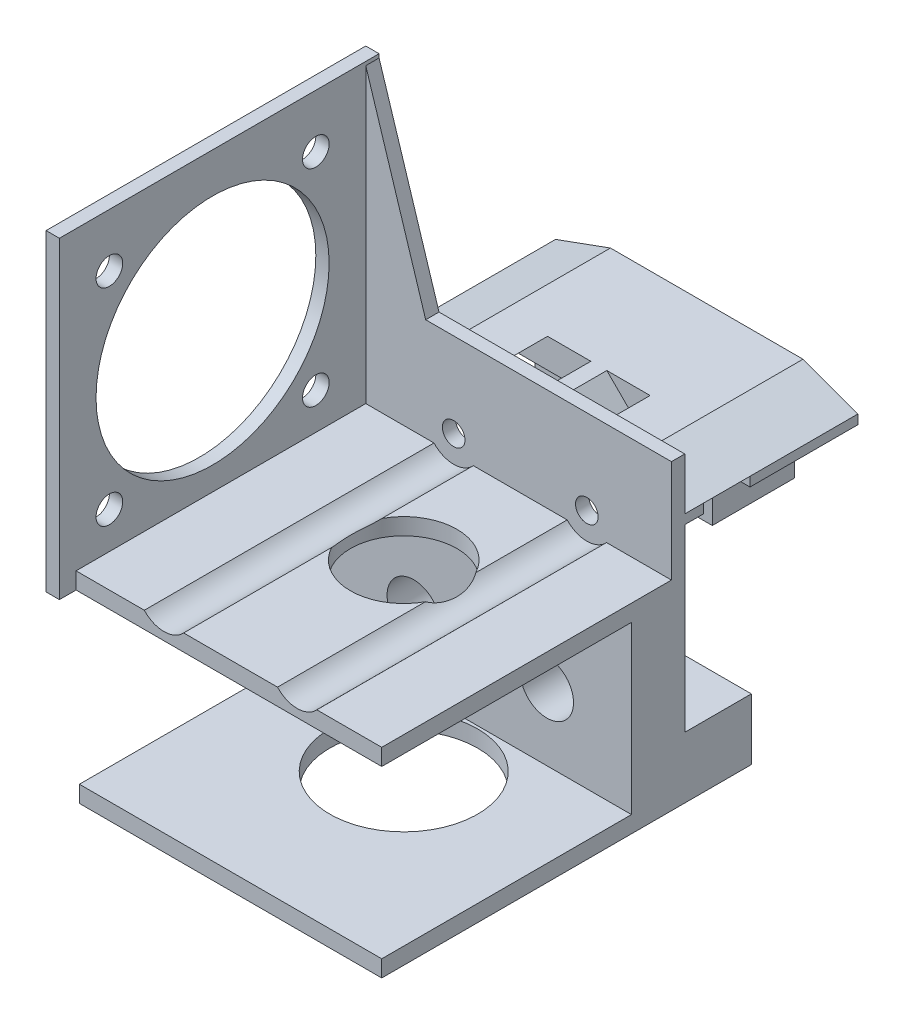
SolidWorks part; units mm, degrees
ref_plane "Front Plane" through (0, 0, 0) normal (0, 0, 1) x (1, 0, 0)
ref_plane "Top Plane" through (0, 0, 0) normal (0, 1, 0) x (1, 0, 0)
ref_plane "Right Plane" through (0, 0, 0) normal (1, 0, 0) x (0, 0, -1)
sketch "Sketch1" plane through (0, 0, 0) normal (0, 0, 1) x (1, 0, 0)
  line L1 (0, 0) -> (45.4, 0)
  line L2 (0, 0) -> (0, 45.4)
  line L3 (0, 45.4) -> (45.4, 45.4)
  line L4 (45.4, 0) -> (45.4, 45.4)
  dimension "D1" = 45.4
  dimension "D2" = 45.4
extrude "Boss-Extrude1" add sketch "Sketch1" along normal blind 12
sketch "Sketch2" plane through (0, 0, 0) normal (0, 0, -1) x (-1, 0, 0)
  line L0 (-45.4, 0) -> (-45.4, 45.4) construction
  line L1 (-45.4, 36.2) -> (0, 36.2)
  line L2 (-45.4, 36.2) -> (-45.4, 9.2)
  line L3 (-45.4, 9.2) -> (0, 9.2)
  line L4 (0, 36.2) -> (0, 9.2)
  line L5 (0, 45.4) -> (0, 0) construction
  line L6 (-45.4, 22.7) -> (0, 22.7) construction
  point P13 (-45.4, 22.7)
  dimension "D1" = 27
extrude "Cut-Extrude1" cut sketch "Sketch2" against normal blind 10
sketch "Sketch13" plane through (0, 0, 12) normal (0, 0, 1) x (1, 0, 0)
  line L0 (22.7, 45.4) -> (22.7, 0) construction
  line L1 (32.7, 12.7) -> (12.7, 12.7) construction
  line L2 (32.7, 12.7) -> (32.7, 32.7) construction
  line L3 (32.7, 32.7) -> (12.7, 32.7) construction
  line L4 (12.7, 12.7) -> (12.7, 32.7) construction
  line L5 (32.7, 12.7) -> (12.7, 32.7) construction
  line L6 (32.7, 32.7) -> (12.7, 12.7) construction
  line L7 (45.4, 45.4) -> (0, 45.4) construction
  line L8 (0, 0) -> (45.4, 0) construction
  line L9 (0, 22.7) -> (45.4, 22.7) construction
  line L10 (0, 9.2) -> (0, 36.2) construction
  line L11 (45.4, 36.2) -> (45.4, 9.2) construction
  circle A4 centre (32.7, 32.7) radius 1.7
  circle A5 centre (12.7, 32.7) radius 1.7
  circle A6 centre (32.7, 12.7) radius 1.7
  circle A7 centre (12.7, 12.7) radius 1.7
  point P12 (22.7, 22.7)
  point P31 (22.7, 22.7)
  dimension "D1" = 3.4
  dimension "D2" = 20
  dimension "D3" = 20
extrude "Cut-Extrude4" cut sketch "Sketch13" against normal up to next
sketch "Sketch20" plane through (45.4, 0, 0) normal (1, 0, 0) x (0, 0, -1)
  line L1 (-7.2, 36.2) -> (-0.2, 36.2)
  line L2 (-7.2, 36.2) -> (-7.2, 37.6)
  line L3 (-7.2, 37.6) -> (-0.2, 37.6)
  line L4 (-0.2, 36.2) -> (-0.2, 37.6)
  line L5 (-10, 36.2) -> (0, 36.2) construction
  line L6 (0, 36.2) -> (0, 45.4) construction
  dimension "D1" = 1.4
  dimension "D2" = 0.2
  dimension "D3" = 7
extrude "Cut-Extrude10" cut sketch "Sketch20" against normal blind 15
sketch "Sketch21" plane through (45.4, 0, 0) normal (1, 0, 0) x (0, 0, -1)
  line L0 (-0.2, 37.6) -> (-7.2, 37.6) construction
  line L1 (0, 45.4) -> (-10, 45.4)
  line L2 (0, 45.4) -> (0, 40.6)
  line L3 (0, 40.6) -> (-10, 40.6)
  line L4 (-10, 45.4) -> (-10, 40.6)
  dimension "D1" = 10
  dimension "D2" = 3
extrude "Cut-Extrude11" cut sketch "Sketch21" against normal through all
sketch "Sketch22" plane through (0, 0, 0) normal (-1, 0, 0) x (0, 0, 1)
  line L0 (10, 36.2) -> (0, 36.2) construction
  line L1 (0.2, 36.2) -> (7.2, 36.2)
  line L2 (0.2, 36.2) -> (0.2, 37.6)
  line L3 (0.2, 37.6) -> (7.2, 37.6)
  line L4 (7.2, 36.2) -> (7.2, 37.6)
  line L5 (0, 40.6) -> (0, 36.2) construction
  dimension "D1" = 7
  dimension "D2" = 0.2
  dimension "D3" = 1.4
extrude "Cut-Extrude12" cut sketch "Sketch22" against normal blind 15
sketch "Sketch29" plane through (0, 0, 12) normal (0, 0, 1) x (1, 0, 0)
  line L0 (0, 0) -> (45.4, 0) construction
  line L1 (0, 0) -> (45.4, 0)
  line L2 (0, 0) -> (0, 30)
  line L3 (0, 30) -> (45.4, 30)
  line L4 (45.4, 0) -> (45.4, 30)
  line L5 (0, 45.4) -> (0, 0) construction
  line L7 (22.7, 45.4) -> (22.7, 0) construction
  line L8 (45.4, 45.4) -> (0, 45.4) construction
  dimension "D3" = 30
extrude "Boss-Extrude6" add sketch "Sketch29" along normal blind 43.5
sketch "Sketch26" plane through (0, 0, 0) normal (0, 0, -1) x (-1, 0, 0)
  line L1 (-45.4, 40.6) -> (0, 40.6)
  line L2 (-45.4, 40.6) -> (-45.4, 36.2)
  line L3 (-45.4, 36.2) -> (0, 36.2)
  line L4 (0, 40.6) -> (0, 36.2)
  line L5 (0, 36.2) -> (-45.4, 36.2) construction
  line L6 (-45.4, 36.2) -> (-45.4, 40.6) construction
  line L7 (0, 40.6) -> (0, 36.2) construction
  line L8 (0, 40.6) -> (-45.4, 40.6) construction
extrude "Boss-Extrude4" add sketch "Sketch26" along normal blind 16
sketch "Sketch23" plane through (0, 40.6, 0) normal (0, 1, 0) x (1, 0, 0)
  line L1 (30.4, -0.2) -> (28.4, -0.2)
  line L2 (30.4, -0.2) -> (30.4, -7.2)
  line L3 (30.4, -7.2) -> (28.4, -7.2)
  line L4 (28.4, -0.2) -> (28.4, -7.2)
  line L5 (17, -7.2) -> (15, -7.2)
  line L6 (17, -7.2) -> (17, -0.2)
  line L7 (17, -0.2) -> (15, -0.2)
  line L8 (15, -7.2) -> (15, -0.2)
  line L9 (45.4, -10) -> (45.4, 16) construction
  line L10 (0, -10) -> (0, 16) construction
  line L13 (0, -10) -> (45.4, -10) construction
  dimension "D1" = 2
  dimension "D2" = 2
  dimension "D3" = 7
  dimension "D4" = 7
  dimension "D5" = 2.8
  dimension "D7" = 15
  dimension "D8" = 15
extrude "Cut-Extrude13" cut sketch "Sketch23" along normal blind 15 and the other way blind 15
sketch "Sketch17" plane through (0, 0, 12) normal (0, 0, 1) x (1, 0, 0)
  line L1 (12.7, 12.7) -> (32.7, 12.7) construction
  line L2 (12.7, 12.7) -> (12.7, 32.7) construction
  line L3 (12.7, 32.7) -> (32.7, 32.7) construction
  line L4 (32.7, 12.7) -> (32.7, 32.7) construction
  line L5 (12.7, 12.7) -> (32.7, 32.7) construction
  line L6 (12.7, 32.7) -> (32.7, 12.7) construction
  line L9 (22.7, 45.4) -> (22.7, 0) construction
  line L10 (45.4, 45.4) -> (0, 45.4) construction
  circle A0 centre (12.7, 32.7) radius 4
  circle A4 centre (32.7, 32.7) radius 4
  circle A5 centre (32.7, 12.7) radius 4
  circle A6 centre (12.7, 12.7) radius 4
  point P12 (22.7, 22.7)
  dimension "D1" = 8
  dimension "D2" = 20
  dimension "D3" = 20
extrude "Cut-Extrude8" cut sketch "Sketch17" along normal through all
chamfer "Chamfer1" distance 3 angle 70 1 edges at (45.4, 40.6, -3) first distance on face at (45.4, 29.4, 9.8625)
chamfer "Chamfer2" distance 3 angle 70 1 edges at (0, 40.6, -3) first distance on face at (0, 29.4, 9.8625)
sketch "Sketch24" plane through (0, 0, 0) normal (0, 0, -1) x (-1, 0, 0)
  line L0 (0, 0) -> (-45.4, 0) construction
  line L1 (-12, 0) -> (-10, 0)
  line L2 (-12, 0) -> (-12, 9.2)
  line L3 (-12, 9.2) -> (-10, 9.2)
  line L4 (-10, 0) -> (-10, 9.2)
  line L5 (-45.4, 9.2) -> (0, 9.2) construction
  line L6 (0, 9.2) -> (0, 0) construction
  dimension "D1" = 2
  dimension "D2" = 10
extrude "Boss-Extrude2" add sketch "Sketch24" along normal blind 10.25
sketch "Sketch25" plane through (10, 0, 0) normal (-1, 0, 0) x (0, 0, 1)
  line L0 (-10.25, 0) -> (0, 0) construction
  line L1 (-10.25, 9.2) -> (-8.75, 9.2)
  line L2 (-10.25, 9.2) -> (-10.25, 0)
  line L3 (-10.25, 0) -> (-8.75, 0)
  line L4 (-8.75, 9.2) -> (-8.75, 0)
  dimension "D1" = 1.5
extrude "Boss-Extrude3" add sketch "Sketch25" along normal blind 10
fillet "Fillet1" radius 4 2 edges at (12, 4.6, -10.25) (10, 4.6, -8.75)
chamfer "Chamfer3" distance 3 angle 45 2 edges at (15, 37.6, 3.7) (30.4, 37.6, 3.7)
chamfer "Chamfer4" distance 4.5 angle 45 2 edges at (28.4, 40.6, 3.7) (17, 40.6, 3.7)
sketch "Sketch27" plane through (0, 36.2, 0) normal (0, -1, 0) x (1, 0, 0)
  line L0 (45.4, -16) -> (0, -16) construction
  line L1 (35.878, -16) -> (9.2478, -16)
  line L2 (35.878, -16) -> (35.878, -3.6551)
  line L3 (35.878, -3.6551) -> (9.2478, -3.6551)
  line L4 (9.2478, -16) -> (9.2478, -3.6551)
extrude "Boss-Extrude5" add sketch "Sketch27" along normal blind 11.7
sketch "Sketch36" plane through (45.4, 0, 0) normal (1, 0, 0) x (0, 0, -1)
  line L0 (-55.5, 30) -> (-12, 30) construction
  line L1 (-55.5, 27.5) -> (-18, 27.5)
  line L2 (-55.5, 27.5) -> (-55.5, 2.5)
  line L3 (-55.5, 2.5) -> (-18, 2.5)
  line L4 (-18, 27.5) -> (-18, 2.5)
  line L5 (-10, 36.2) -> (-10, 9.2) construction
  line L6 (-55.5, 0) -> (0, 0) construction
  line L7 (-55.5, 0) -> (-55.5, 30) construction
  dimension "D1" = 2.5
  dimension "D2" = 8
  dimension "D3" = 2.5
extrude "Cut-Extrude18" cut sketch "Sketch36" against normal through all
sketch "Sketch28" plane through (0, 24.5, 0) normal (0, -1, 0) x (1, 0, 0)
  circle A0 centre (31.698, -9.7656) radius 1.5
  circle A1 centre (13.6999, -9.7639) radius 1.5
  dimension "D1" = 3
  dimension "D2" = 3
extrude "Cut-Extrude14" cut sketch "Sketch28" against normal blind 10
sketch "Sketch31" plane through (0, 30, 0) normal (0, 1, 0) x (1, 0, 0)
  line L0 (29.7487, -12) -> (15.6513, -12) construction
  line L1 (22.7, -29.5) -> (22.7, -12) construction
  line L3 (45.4, -12) -> (0, -12) construction
  circle A0 centre (22.7, -29.5) radius 8
  dimension "D1" = 16
  dimension "D2" = 17.5
extrude "Cut-Extrude15" cut sketch "Sketch31" against normal blind 35
sketch "Sketch32" plane through (0, 0, 0) normal (0, -1, 0) x (1, 0, 0)
  circle A1 centre (22.7, 29.5) radius 11.1
  dimension "D1" = 22.2
extrude "Cut-Extrude16" cut sketch "Sketch32" against normal up to surface (27.5 mm away) up to face at (14.7, 27.5, 29.5)
sketch "Sketch33" plane through (0, 0, 0) normal (-1, 0, 0) x (0, 0, 1)
  line L1 (10, 45.4) -> (12, 45.4)
  line L2 (10, 45.4) -> (10, 27.5)
  line L4 (12, 45.4) -> (12, 30)
  line L5 (12, 30) -> (55.5, 30)
  line L6 (55.5, 30) -> (55.5, 27.5)
  line L8 (55.5, 27.5) -> (10, 27.5)
  dimension "D1" = 2.5
extrude "Boss-Extrude7" add sketch "Sketch33" along normal blind 0.5
sketch "Sketch34" plane through (-0.5, 0, 0) normal (-1, 0, 0) x (0, 0, 1)
  line L0 (10, 27.5) -> (55.5, 27.5) construction
  line L1 (10, 27.5) -> (58, 27.5)
  line L2 (10, 27.5) -> (10, 74.5)
  line L3 (10, 74.5) -> (58, 74.5)
  line L4 (58, 27.5) -> (58, 74.5)
  line L6 (10, 45.4) -> (10, 27.5) construction
  dimension "D1" = 48
  dimension "D2" = 47
extrude "Boss-Extrude8" add sketch "Sketch34" along normal blind 2
sketch "Sketch35" plane through (-2.5, 0, 0) normal (-1, 0, 0) x (0, 0, 1)
  line L0 (10, 74.5) -> (10, 27.5) construction
  line L1 (19.5, 66.5) -> (50.5, 66.5) construction
  line L2 (19.5, 66.5) -> (19.5, 35.5) construction
  line L3 (19.5, 35.5) -> (50.5, 35.5) construction
  line L4 (50.5, 66.5) -> (50.5, 35.5) construction
  line L5 (10, 27.5) -> (58, 27.5) construction
  line L6 (35, 66.5) -> (35, 35.5) construction
  line L7 (19.5, 51) -> (50.5, 51) construction
  circle A0 centre (19.5, 66.5) radius 2
  circle A1 centre (50.5, 66.5) radius 2
  circle A2 centre (50.5, 35.5) radius 2
  circle A3 centre (19.5, 35.5) radius 2
  circle A4 centre (35, 51) radius 17.5
  point P19 (35, 51)
  dimension "D1" = 35
  dimension "D2" = 4
  dimension "D3" = 31
  dimension "D4" = 9.5
  dimension "D5" = 8
extrude "Cut-Extrude17" cut sketch "Sketch35" against normal blind 10
chamfer "Chamfer7" distance 9 angle 72.5 1 edges at (-0.5, 45.4, 11) first distance on face at (22.45, 45.4, 11)
